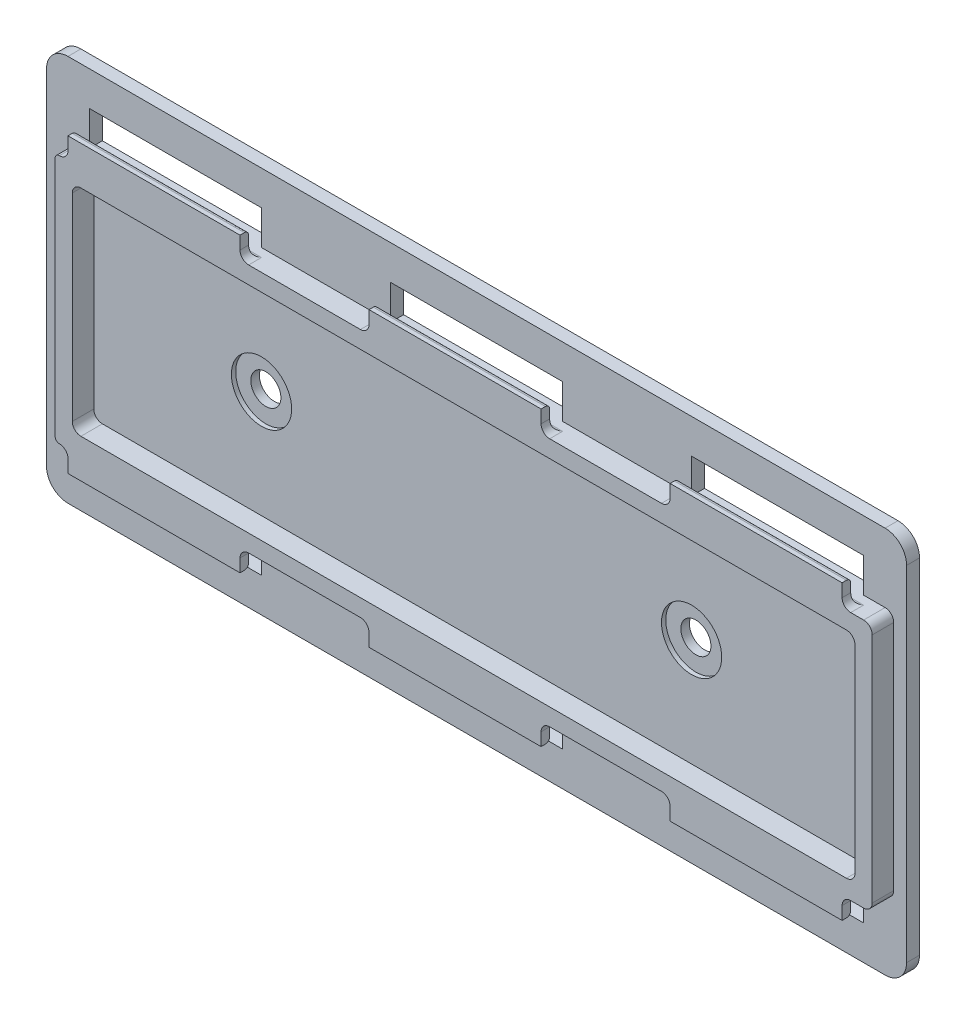
SolidWorks part; units mm, degrees
ref_plane "Plano frontal" through (0, 0, 0) normal (0, 0, 1) x (1, 0, 0)
ref_plane "Plano superior" through (0, 0, 0) normal (0, 1, 0) x (1, 0, 0)
ref_plane "Plano direito" through (0, 0, 0) normal (1, 0, 0) x (0, 0, -1)
sketch "Esboço1" plane through (0, 0, 0) normal (0, 0, 1) x (1, 0, 0)
  line L1 (-50, -22.5) -> (50, -22.5)
  line L2 (-50, -22.5) -> (-50, 22.5)
  line L3 (-50, 22.5) -> (50, 22.5)
  line L4 (50, -22.5) -> (50, 22.5)
  line L5 (-50, -22.5) -> (50, 22.5) construction
  line L6 (-50, 22.5) -> (50, -22.5) construction
  point P0 (0, 0)
  dimension "D1" = 45
  dimension "D2" = 100
extrude "Ressalto-extrusão1" add sketch "Esboço1" along normal blind 1.5
sketch "Esboço2" plane through (0, 0, 1.5) normal (0, 0, 1) x (1, 0, 0)
  line L5 (-50, 22.5) -> (-50, -22.5) construction
  line L6 (-46.5, 14.5) -> (48.5, 14.5)
  line L7 (-46.5, 14.5) -> (-46.5, -14.5)
  line L8 (-46.5, -14.5) -> (48.5, -14.5)
  line L9 (48.5, 14.5) -> (48.5, -14.5)
  line L10 (-50, -22.5) -> (50, -22.5) construction
  line L11 (-44.5, 12.5) -> (46.5, 12.5)
  line L12 (46.5, 12.5) -> (46.5, -12.5)
  line L13 (-44.5, -12.5) -> (46.5, -12.5)
  line L14 (-44.5, 12.5) -> (-44.5, -12.5)
  point P0 (0, 0)
  dimension "D1" = 29
  dimension "D2" = 3.5
  dimension "D3" = 95
  dimension "D4" = 8
  dimension "D5" = 2
extrude "Ressalto-extrusão3" add sketch "Esboço2" along normal blind 2.5
sketch "Esboço3" plane through (0, 0, 1.5) normal (0, 0, 1) x (1, 0, 0)
  line L0 (-46.5, -14.5) -> (48.5, -14.5) construction
  line L1 (-45, -14.5) -> (-25, -14.5)
  line L2 (-45, -14.5) -> (-45, -17.5)
  line L3 (-45, -17.5) -> (-25, -17.5)
  line L4 (-25, -14.5) -> (-25, -17.5)
  line L5 (-46.5, 14.5) -> (-46.5, -14.5) construction
  line L6 (25, -14.5) -> (45, -14.5)
  line L7 (25, -14.5) -> (25, -17.5)
  line L8 (25, -17.5) -> (45, -17.5)
  line L9 (45, -14.5) -> (45, -17.5)
  line L10 (-10, -14.5) -> (10, -14.5)
  line L11 (-10, -14.5) -> (-10, -17.5)
  line L12 (-10, -17.5) -> (10, -17.5)
  line L13 (10, -14.5) -> (10, -17.5)
  line L14 (-20.2295, 0) -> (12.773, 0) construction
  line L15 (25, 17.5) -> (45, 17.5)
  line L16 (45, 14.5) -> (45, 17.5)
  line L17 (25, 14.5) -> (45, 14.5)
  line L18 (25, 14.5) -> (25, 17.5)
  line L19 (-10, 17.5) -> (10, 17.5)
  line L20 (10, 14.5) -> (10, 17.5)
  line L21 (-10, 14.5) -> (10, 14.5)
  line L22 (-10, 14.5) -> (-10, 17.5)
  line L23 (-45, 17.5) -> (-25, 17.5)
  line L24 (-25, 14.5) -> (-25, 17.5)
  line L25 (-45, 14.5) -> (-25, 14.5)
  line L26 (-45, 14.5) -> (-45, 17.5)
  point P16 (-25, -16)
  dimension "D1" = 20
  dimension "D2" = 20
  dimension "D3" = 20
  dimension "D4" = 1.5
  dimension "D5" = 3
  dimension "D6" = 3
  dimension "D7" = 3
  dimension "D8" = 15
  dimension "D9" = 15
extrude "Ressalto-extrusão6" add sketch "Esboço3" along normal blind 2.5
fillet "Filete7" radius 1 1 edges at (25, -14.5, 2.75) type face fillet first side face at (25, -16, 2.75) second side face at (17.5, -14.5, 2.75)
fillet "Filete8" radius 1 1 edges at (10, -14.5, 2.75) type face fillet first side face at (10, -16, 2.75) second side face at (17, -14.5, 2.75)
fillet "Filete9" radius 1 1 edges at (-10, -14.5, 2.75) type face fillet first side face at (-10, -16, 2.75) second side face at (-17.5, -14.5, 2.75)
fillet "Filete10" radius 1 1 edges at (-25, -14.5, 2.75) type face fillet first side face at (-25, -16, 2.75) second side face at (-18, -14.5, 2.75)
fillet "Filete11" radius 1 1 edges at (-45, -14.5, 2.75) type face fillet first side face at (-45, -16, 2.75) second side face at (-45.75, -14.5, 2.75)
sketch "Esboço4" plane through (-45, 0, 0) normal (-1, 0, 0) x (0, 0, 1)
  line L1 (1.5, -17.5) -> (2.5, -17.5)
  line L2 (1.5, -17.5) -> (1.5, -14.5001)
  line L3 (1.5, -14.5001) -> (2.5, -14.5001)
  line L4 (2.5, -17.5) -> (2.5, -14.5001)
  dimension "D1" = 1
extrude "Corte-extrusão1" cut sketch "Esboço4" against normal mid plane 229.5
sketch "Esboço5" plane through (-45, 0, 0) normal (-1, 0, 0) x (0, 0, 1)
  line L0 (4, 17.5) -> (1.5, 17.5) construction
  line L1 (1.5, 14.5) -> (2.5, 14.5)
  line L2 (1.5, 14.5) -> (1.5, 17.5)
  line L3 (1.5, 17.5) -> (2.5, 17.5)
  line L4 (2.5, 14.5) -> (2.5, 17.5)
  dimension "D1" = 1
extrude "Corte-extrusão2" cut sketch "Esboço5" against normal blind 92.5
fillet "Filete14" radius 1 1 edges at (45, 14.5, 3.25) type face fillet first side face at (45, 16, 3.25) second side face at (0.25, 14.5, 3.125)
fillet "Filete15" radius 1 1 edges at (25, 14.5, 3.25) type face fillet first side face at (25, 16, 3.25) second side face at (0.375, 14.5, 3.125)
fillet "Filete16" radius 1 1 edges at (10, 14.5, 3.25) type face fillet first side face at (10, 16, 3.25) second side face at (0.25, 14.5, 3.125)
fillet "Filete17" radius 1 1 edges at (-10, 14.5, 3.25) type face fillet first side face at (-10, 16, 3.25) second side face at (0.375, 14.5, 3.125)
fillet "Filete18" radius 1 1 edges at (-25, 14.5, 3.25) type face fillet first side face at (-25, 16, 3.25) second side face at (0.25, 14.5, 3.125)
fillet "Filete19" radius 1 1 edges at (-45, 14.5, 3.25) type face fillet first side face at (-45, 16, 3.25) second side face at (0.375, 14.5, 3.125)
fillet "Filete20" radius 0.5 1 edges at (35, 14.5, 2.5) type face fillet first side face at (35, 15.7643, 2.5) second side face at (0.25, 14.5, 3.125)
fillet "Filete21" radius 0.5 1 edges at (0, 14.5, 2.5) type face fillet first side face at (0, 15.7643, 2.5) second side face at (0.25, 14.5, 3.0625)
fillet "Filete22" radius 0.5 1 edges at (-35, 14.5, 2.5) type face fillet first side face at (0.25, 14.5, 3) second side face at (-35, 15.7643, 2.5)
fillet "Filete23" radius 0.5 1 edges at (-35, -14.5001, 2.5) type face fillet first side face at (-35, -15.7657, 2.5) second side face at (-35, -14.5001, 2)
fillet "Filete24" radius 0.5 1 edges at (0, -14.5001, 2.5) type face fillet first side face at (0, -14.5001, 2) second side face at (0, -15.7657, 2.5)
fillet "Filete25" radius 0.5 1 edges at (34.5058, -14.5001, 2.5) type face fillet first side face at (32.8434, -15.8594, 2.5) second side face at (34.5058, -14.5001, 2)
fillet "Filete26" radius 2.5 1 edges at (-50, -22.5, 0.75) type face fillet first side face at (-50, 0, 0.75) second side face at (0, -22.5, 0.75)
fillet "Filete27" radius 2.5 1 edges at (50, -22.5, 0.75) type face fillet first side face at (50, 0, 0.75) second side face at (1.25, -22.5, 0.75)
fillet "Filete28" radius 2.5 1 edges at (50, 22.5, 0.75) type face fillet first side face at (0, 22.5, 0.75) second side face at (50, 1.25, 0.75)
fillet "Filete29" radius 2.5 1 edges at (-50, 22.5, 0.75) type face fillet first side face at (-50, 1.25, 0.75) second side face at (-1.25, 22.5, 0.75)
sketch "Esboço6" plane through (0, 0, 1.5) normal (0, 0, 1) x (1, 0, 0)
  line L0 (0, 0) -> (50, 0) construction
  circle A0 centre (25, 0) radius 1.75
  circle A1 centre (-25, 0) radius 1.75
  dimension "D1" = 25
  dimension "D2" = 25
  dimension "D3" = 3.5
  dimension "D4" = 3.5
extrude "Corte-extrusão3" cut sketch "Esboço6" against normal blind 92.5
fillet "Filete30" radius 1 1 edges at (48.5, -14.5, 2.75) type face fillet first side face at (46.75, -14.5, 2.75) second side face at (48.5, 0, 2.75)
fillet "Filete31" radius 1 1 edges at (48.5, 14.5, 2.75) type face fillet first side face at (0.25, 14.5, 2.9375) second side face at (48.5, 0.5, 2.75)
fillet "Filete32" radius 0.5 1 edges at (-46.5, -14.5, 2.75) type face fillet first side face at (-46.5, 0, 2.75) second side face at (-46.25, -14.5, 2.75)
fillet "Filete33" radius 0.5 1 edges at (-46.5, 14.5, 2.75) type face fillet first side face at (0.125, 14.5, 2.9375) second side face at (-46.5, 0.25, 2.75)
fillet "Filete34" radius 1 1 edges at (45, -14.5, 2.75) type face fillet first side face at (46.25, -14.5, 2.75) second side face at (45, -15.4138, 2.5862)
fillet "Filete35" radius 1 1 edges at (46.5, 12.5, 2.75) type face fillet first side face at (1, 12.5, 2.75) second side face at (46.5, 0, 2.75)
fillet "Filete36" radius 1 1 edges at (46.5, -12.5, 2.75) type face fillet first side face at (46.5, -0.5, 2.75) second side face at (1, -12.5, 2.75)
fillet "Filete37" radius 1 1 edges at (-44.5, 12.5, 2.75) type face fillet first side face at (0.5, 12.5, 2.75) second side face at (-44.5, 0, 2.75)
fillet "Filete38" radius 1 1 edges at (-44.5, -12.5, 2.75) type face fillet first side face at (-44.5, -0.5, 2.75) second side face at (0.5, -12.5, 2.75)
sketch "Esboço7" plane through (0, 0, 1.5) normal (0, 0, 1) x (1, 0, 0)
  circle A0 centre (-25, 0) radius 3.5
  circle A1 centre (25, 0) radius 3.5
extrude "Corte-extrusão5" cut sketch "Esboço7" along normal blind 0.5 and the other way blind 0.5
fillet "Filete39" radius 0.5 1 edges at (-35, 17.5, 2.5) type face fillet first side face at (-35, 15.9971, 2.5) second side face at (-35, 17.5, 3.25)
fillet "Filete40" radius 0.5 1 edges at (35, 17.5, 2.5) type face fillet first side face at (35, 15.9971, 2.5) second side face at (35, 17.5, 3.25)
fillet "Filete41" radius 0.5 1 edges at (0, 17.5, 2.5) type face fillet first side face at (0, 15.9971, 2.5) second side face at (0, 17.5, 3.25)
fillet "Filete42" radius 0.5 1 edges at (-35, -17.5, 2.5) type face fillet first side face at (-35, -15.9971, 2.5) second side face at (-35, -17.5, 3.25)
fillet "Filete43" radius 0.5 1 edges at (0, -17.5, 2.5) type face fillet first side face at (0, -15.9971, 2.5) second side face at (0, -17.5, 3.25)
fillet "Filete44" radius 0.5 1 edges at (35, -17.5, 2.5) type face fillet first side face at (37.5865, -15.598, 2.5) second side face at (35, -17.5, 3.25)
sketch "Esboço8" plane through (0, 0, 1.5) normal (0, 0, 1) x (1, 0, 0)
  line L0 (45, 15.5) -> (45, 17.5) construction
  line L1 (-45, 14.5) -> (-25, 14.5)
  line L2 (-45, 14.5) -> (-45, 18.5)
  line L3 (-45, 18.5) -> (-25, 18.5)
  line L4 (-25, 14.5) -> (-25, 18.5)
  line L5 (-9.9815, 14.5) -> (10.0185, 14.5)
  line L6 (-9.9815, 14.5) -> (-9.9815, 18.5)
  line L7 (-9.9815, 18.5) -> (10.0185, 18.5)
  line L8 (10.0185, 14.5) -> (10.0185, 18.5)
  line L9 (25, 14.5) -> (45, 14.5)
  line L10 (25, 14.5) -> (25, 18.5)
  line L11 (25, 18.5) -> (45, 18.5)
  line L12 (45, 14.5) -> (45, 18.5)
  line L13 (24, 14.5) -> (11, 14.5) construction
  line L14 (-11, 14.5) -> (-24, 14.5) construction
  line L15 (0, 0) -> (-14.0161, 0) construction
  dimension "D1" = 20
  dimension "D2" = 20
  dimension "D3" = 20
  dimension "D4" = 4
  dimension "D5" = 4
  dimension "D6" = 4
extrude "Corte-extrusão15" cut sketch "Esboço8" against normal blind 10
sketch "Esboço10" plane through (0, 0, 0) normal (0, 0, -1) x (-1, 0, 0)
  line L0 (0, 0) -> (-13.7433, 0) construction
  line L1 (-45, 18.5) -> (-25, 18.5)
  line L2 (-45, 18.5) -> (-45, 14.5)
  line L3 (-45, 14.5) -> (-25, 14.5)
  line L4 (-25, 18.5) -> (-25, 14.5)
  line L5 (-10.0185, 18.5) -> (9.9815, 18.5)
  line L6 (-10.0185, 18.5) -> (-10.0185, 14.5)
  line L7 (-10.0185, 14.5) -> (9.9815, 14.5)
  line L8 (9.9815, 18.5) -> (9.9815, 14.5)
  line L9 (25, 18.5) -> (45, 18.5)
  line L10 (25, 18.5) -> (25, 14.5)
  line L11 (25, 14.5) -> (45, 14.5)
  line L12 (45, 18.5) -> (45, 14.5)
  line L13 (25, -14.5) -> (45, -14.5)
  line L14 (45, -18.5) -> (45, -14.5)
  line L15 (25, -18.5) -> (45, -18.5)
  line L16 (25, -18.5) -> (25, -14.5)
  line L17 (-10.0185, -14.5) -> (9.9815, -14.5)
  line L18 (9.9815, -18.5) -> (9.9815, -14.5)
  line L19 (-10.0185, -18.5) -> (9.9815, -18.5)
  line L20 (-10.0185, -18.5) -> (-10.0185, -14.5)
  line L21 (-45, -14.5) -> (-25, -14.5)
  line L22 (-25, -18.5) -> (-25, -14.5)
  line L23 (-45, -18.5) -> (-25, -18.5)
  line L24 (-45, -18.5) -> (-45, -14.5)
extrude "Corte-extrusão19" cut sketch "Esboço10" against normal blind 2.5
sketch "Esboço11" plane through (0, 0, 0) normal (1, 0, 0) x (0, 0, -1)
  line L0 (-2.5, 17) -> (-4.4719, 17)
  line L1 (-4.4719, 17) -> (-4.4719, -17)
  line L2 (-4.4719, -17) -> (-2.391, -17)
  line L3 (-2.391, -17) -> (-2.391, -17.7056)
  line L4 (-2.391, -17.7056) -> (-4.9697, -17.7056)
  line L5 (-4.9697, -17.7056) -> (-4.9697, 18.2772)
  line L6 (-4.9697, 18.2772) -> (-2.391, 18.2772)
  line L7 (-2.391, 18.2772) -> (-2.391, 17)
  line L8 (-2.391, 17) -> (-2.5, 17)
  line L11 (-4, -17.5) -> (-3, -17.5) construction
  dimension "D1" = 0.5
extrude "Corte-extrusão20" cut sketch "Esboço11" against normal mid plane 102
fillet "Filete45" radius 0.5 1 edges at (35, -17, 2.5) type face fillet first side face at (35, -17, 3.25) second side face at (32.5865, -15.473, 2.5)
fillet "Filete46" radius 0.5 1 edges at (0, -17, 2.5) type face fillet first side face at (0, -17, 3.25) second side face at (0.0074, -15.3983, 2.5)
fillet "Filete47" radius 0.5 1 edges at (-35, -17, 2.5) type face fillet first side face at (-35, -17, 3.25) second side face at (-35, -15.3983, 2.5)
fillet "Filete48" radius 0.5 1 edges at (35, 17, 2.5) type face fillet first side face at (35, 17, 3.25) second side face at (35, 15.3982, 2.5)
fillet "Filete49" radius 0.5 1 edges at (0, 17, 2.5) type face fillet first side face at (0, 17, 3.25) second side face at (0.0074, 15.3982, 2.5)
fillet "Filete50" radius 0.5 1 edges at (-35, 17, 2.5) type face fillet first side face at (-35, 17, 3.25) second side face at (-35, 15.3982, 2.5)
sketch "Esboço13" plane through (0, 0, 0) normal (1, 0, 0) x (0, 0, -1)
  line L0 (-3, 16.5) -> (-3, 15)
  line L1 (-2, 14.5) -> (-4, 14.5) construction
  line L2 (-2.5, 14.5) -> (-2, 14.5)
  line L3 (-2, 14.5) -> (-2, 17.3993)
  line L4 (-2, 17.3993) -> (-4.4232, 17.3993)
  line L5 (-4.4232, 17.3993) -> (-4.4232, 16.2545)
  line L6 (-3.5, 17) -> (-4, 17)
  line L7 (-4, 17) -> (-4, 16.25)
  line L8 (-4, 15.5) -> (-4, 17) construction
  line L9 (0, 0) -> (-5.5632, 0) construction
  line L10 (-4.4232, 16.2545) -> (-4.4232, -16.2545)
  line L11 (-4, 16.25) -> (-4, -16.25)
  line L12 (-4, -13.5) -> (-4, 13.5) construction
  line L13 (-3.5, -17) -> (-4, -17)
  line L14 (-4, -17) -> (-4, -16.25)
  line L15 (-2.5, -14.5) -> (-2, -14.5)
  line L16 (-3, -16.5) -> (-3, -15)
  line L17 (-4.4232, -17.3993) -> (-4.4232, -16.2545)
  line L18 (-2, -17.3993) -> (-4.4232, -17.3993)
  line L19 (-2, -14.5) -> (-2, -17.3993)
  arc A0 (-3, 15) -> (-2.5, 14.5) centre (-2.5, 15) ccw
  arc A1 (-3, 16.5) -> (-3.5, 17) centre (-3.5, 16.5) ccw
  arc A2 (-3, -15) -> (-2.5, -14.5) centre (-2.5, -15) cw
  arc A3 (-3, -16.5) -> (-3.5, -17) centre (-3.5, -16.5) cw
  point P16 (-3, 14.5)
  point P19 (-3, 17)
  point P28 (-4, 0)
  point P38 (-4.4232, 0)
  dimension "D1" = 0.5
  dimension "D2" = 0.5
extrude "Corte-extrusão24" cut sketch "Esboço13" against normal mid plane 98 contours L11 L14 L13 A3 L16 A2 L15 L19 L18 L17 L10 L5 L4 L3 L2 A0 L0 A1 L6 L7
